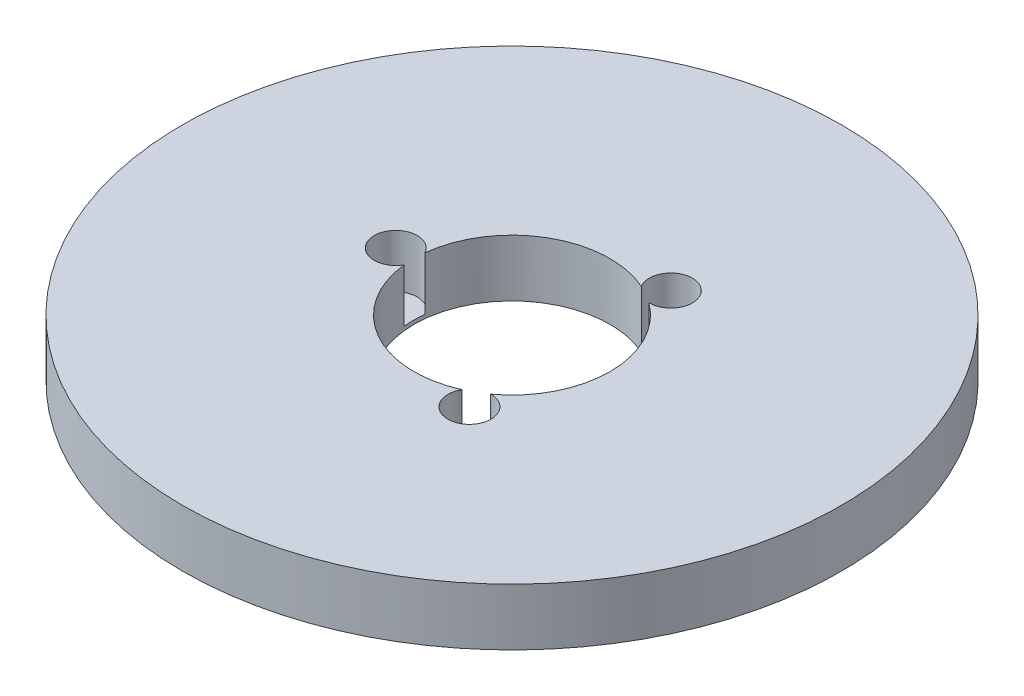
SolidWorks part; units mm, degrees
ref_plane "Front Plane" through (0, 0, 0) normal (0, 0, 1) x (1, 0, 0)
ref_plane "Top Plane" through (0, 0, 0) normal (0, 1, 0) x (1, 0, 0)
ref_plane "Right Plane" through (0, 0, 0) normal (1, 0, 0) x (0, 0, -1)
sketch "Sketch1" plane through (0, 0, 0) normal (0, 1, 0) x (1, 0, 0)
  circle A0 centre (0, 0) radius 92.5
  dimension "FLANGE_OD" = 185
extrude "Boss-Extrude1" add sketch "Sketch1" along normal blind 16
sketch "Sketch2" plane through (0, 0, 0) normal (0, 1, 0) x (1, 0, 0)
  circle A0 centre (0, 0) radius 27.5
  dimension "BORE_D" = 55
extrude "Cut-Extrude1" cut sketch "Sketch2" along normal through all
sketch "Sketch3" plane through (0, 16, 0) normal (0, 1, 0) x (1, 0, 0)
  circle A0 centre (0, 0) radius 32.635 construction
  circle A1 centre (-32.635, 0) radius 6.0473
  dimension "BOLT_D" = 12.0945
  dimension "BOLT_PCD" = 65.2699
extrude "Cut-Extrude2" cut sketch "Sketch3" against normal blind 14.9261
pattern_circular "CirPattern1" count 3 over 360 about axis through (0, 0, 0) along (0, 1, 0) of "Cut-Extrude2"
